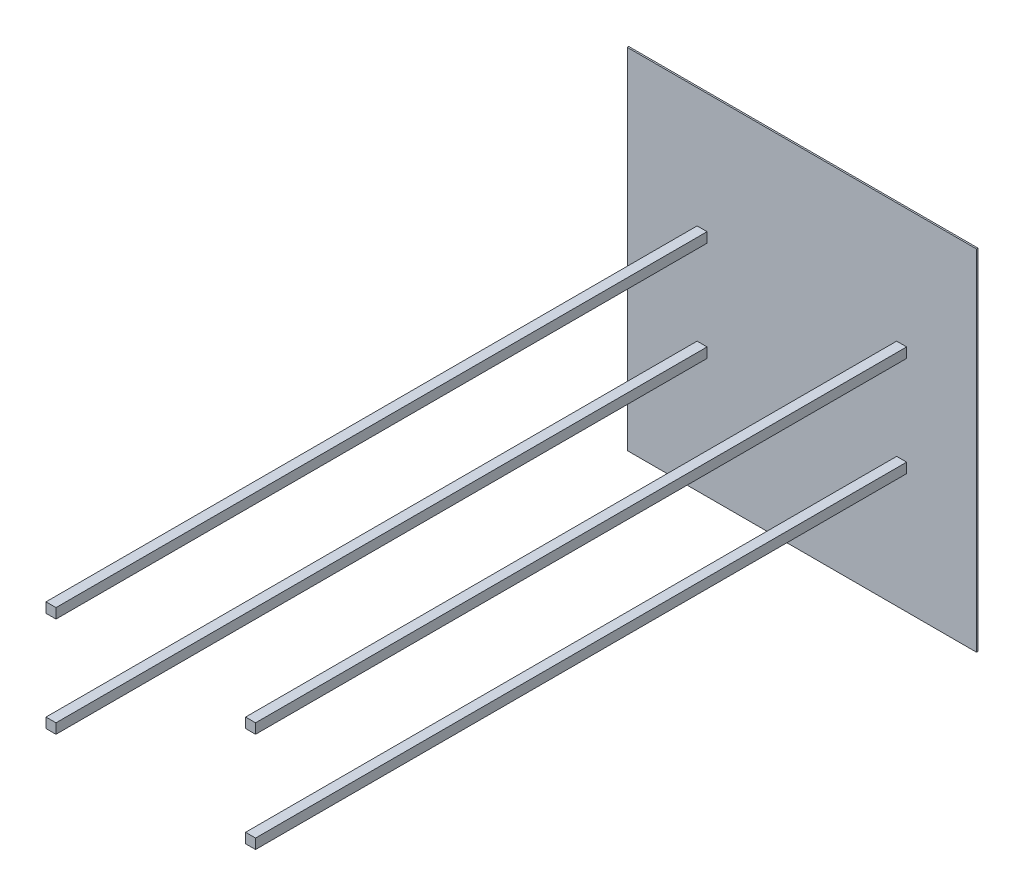
SolidWorks part; units mm, degrees
ref_plane "Piano frontale" through (0, 0, 0) normal (0, 0, 1) x (1, 0, 0)
ref_plane "Piano superiore" through (0, 0, 0) normal (0, 1, 0) x (1, 0, 0)
ref_plane "Piano destro" through (0, 0, 0) normal (1, 0, 0) x (0, 0, -1)
sketch "Schizzo1" plane through (0, 0, 0) normal (0, 0, 1) x (1, 0, 0)
  line L1 (-350, -350) -> (350, -350)
  line L2 (-350, -350) -> (-350, 350)
  line L3 (-350, 350) -> (350, 350)
  line L4 (350, -350) -> (350, 350)
  line L5 (-350, -350) -> (350, 350) construction
  line L6 (-350, 350) -> (350, -350) construction
  point P0 (0, 0)
  dimension "D1" = 700
  dimension "D2" = 700
extrude "Estrusione-Estrusione1" add sketch "Schizzo1" along normal blind 3
sketch "Schizzo2" plane through (0, 0, 3) normal (0, 0, 1) x (1, 0, 0)
  line L1 (200, -100) -> (-200, -100) construction
  line L2 (200, -100) -> (200, 100) construction
  line L3 (200, 100) -> (-200, 100) construction
  line L4 (-200, -100) -> (-200, 100) construction
  line L5 (200, -100) -> (-200, 100) construction
  line L6 (200, 100) -> (-200, -100) construction
  line L7 (-210, 90) -> (-190, 90)
  line L8 (-210, 90) -> (-210, 110)
  line L9 (-210, 110) -> (-190, 110)
  line L10 (-190, 90) -> (-190, 110)
  line L11 (-210, 90) -> (-190, 110) construction
  line L12 (-210, 110) -> (-190, 90) construction
  point P0 (0, 0)
  dimension "D1" = 400
  dimension "D2" = 200
  dimension "D3" = 20
  dimension "D4" = 20
extrude "Estrusione-Estrusione2" add sketch "Schizzo2" along normal blind 1305
pattern_linear "Ripetizione a L1" count 2 spacing 400 along (1, 0, 0) of "Estrusione-Estrusione2"
pattern_linear "Ripetizione a L2" count 2 spacing 200 along (0, -1, 0) of "Ripetizione a L1"
